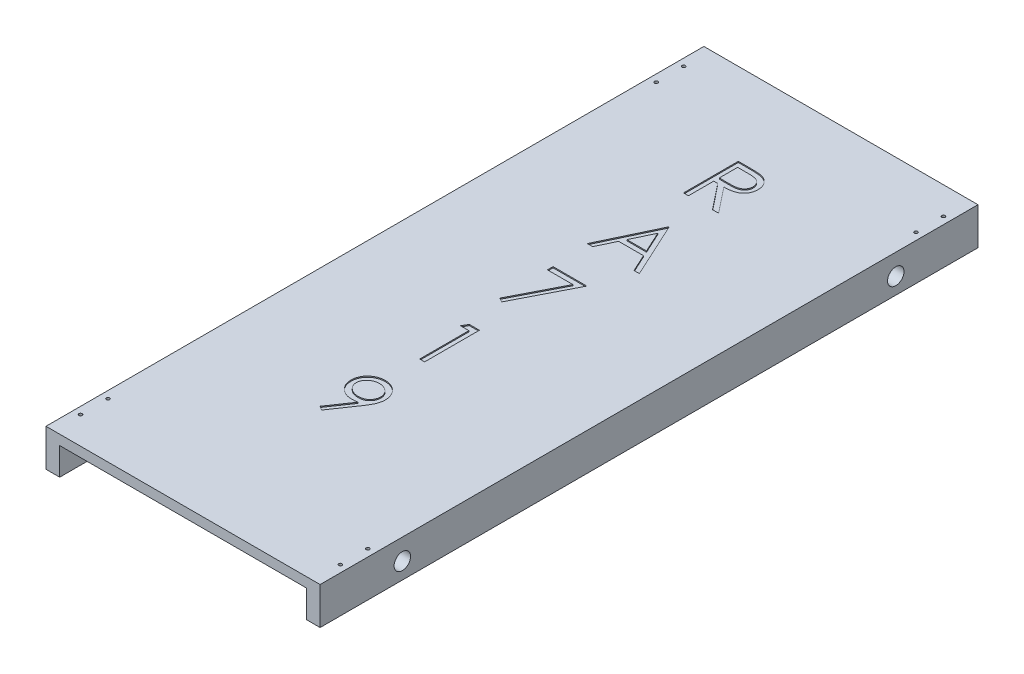
SolidWorks part; units mm, degrees
material "Cedar"
ref_plane "Front Plane" through (0, 0, 0) normal (0, 0, 1) x (1, 0, 0)
ref_plane "Top Plane" through (0, 0, 0) normal (0, 1, 0) x (1, 0, 0)
ref_plane "Right Plane" through (0, 0, 0) normal (1, 0, 0) x (0, 0, -1)
sketch "Sketch2" plane through (0, 0, 0) normal (0, 0, 1) x (1, 0, 0)
  line L0 (0, 0) -> (0, 68)
  line L1 (0, 68) -> (500, 68)
  line L2 (0, 0) -> (25, 0)
  line L3 (25, 50) -> (475, 50)
  line L4 (25, 50) -> (25, 0)
  line L5 (500, 68) -> (500, 0)
  line L6 (500, 0) -> (475, 0)
  line L7 (475, 0) -> (475, 50)
  dimension "D1" = 68
  dimension "D2" = 500
  dimension "D3" = 25
  dimension "D4" = 50
  dimension "D5" = 68
  dimension "D6" = 25
  dimension "D7" = 50
extrude "Boss-Extrude1" add sketch "Sketch2" along normal blind 1200
sketch "Sketch3" plane through (500, 0, 0) normal (1, 0, 0) x (0, 0, -1)
  line L1 (-1200, 0) -> (0, 0) construction
  line L2 (-1200, 0) -> (-1200, 68) construction
  line L3 (0, 0) -> (0, 68) construction
  circle A0 centre (-1050, 30) radius 15
  circle A1 centre (-150, 30) radius 15
  dimension "D1" = 30
  dimension "D3" = 30
  dimension "D4" = 30
  dimension "D2" = 150
  dimension "D5" = 150
  dimension "D6" = 30
extrude "Cut-Extrude1" cut sketch "Sketch3" against normal through all
sketch "Sketch4" plane through (0, 68, 0) normal (0, 1, 0) x (1, 0, 0)
  line L0 (0, -1200) -> (0, 0) construction
  line L1 (500, 0) -> (0, 0) construction
  text T0 "R\r\nA\r\n7\r\n1\r\n9" font "Century Gothic" height 100
  dimension "D1" = 200
  dimension "D2" = 250
extrude "Cut-Extrude2" cut sketch "Sketch4" against normal blind 2
sketch "Sketch5" plane through (0, 50, 0) normal (0, -1, 0) x (1, 0, 0)
  line L0 (0, 1200) -> (0, 0) construction
  line L1 (25, 1200) -> (475, 1200) construction
  text T0 "R\r\nA\r\n7\r\n1\r\n9" font "Century Gothic" height 100
  dimension "D1" = 200
  dimension "D2" = 250
extrude "Cut-Extrude3" cut sketch "Sketch5" against normal blind 2
hole_wizard "Ø6.0 (6) Diameter Hole1" positions "Sketch8" profile "Sketch7" hole size "Ø6.0" standard "ISO" end condition through all
sketch "Sketch8" plane through (0, 0, 0) normal (0, -1, 0) x (-1, 0, 0)
  line L0 (-475, -1200) -> (-500, -1200) construction
  line L1 (-500, -1200) -> (-500, 0) construction
  line L2 (-475, 0) -> (-500, 0) construction
  line L3 (0, 0) -> (-25, 0) construction
  line L4 (0, -1200) -> (0, 0) construction
  line L5 (0, -1200) -> (-25, -1200) construction
  point P0 (-487, -1150)
  point P8 (-487, -1100)
  point P11 (-487, -50)
  point P13 (-487, -100)
  point P18 (-13, -50)
  point P20 (-13, -100)
  point P27 (-13, -1150)
  point P29 (-13, -1100)
  dimension "D1" = 50
  dimension "D2" = 13
  dimension "D3" = 100
  dimension "D4" = 13
  dimension "D5" = 50
  dimension "D6" = 100
  dimension "D7" = 13
  dimension "D8" = 13
  dimension "D9" = 50
  dimension "D10" = 100
  dimension "D11" = 13
  dimension "D12" = 13
  dimension "D13" = 50
  dimension "D14" = 100
  dimension "D15" = 13
  dimension "D16" = 13
sketch "Sketch7" plane through (487, 0, 1150) normal (1, 0, 0) x (0, 0, -1)
  line L0 (0, 0) -> (0, 68)
  line L1 (0, 68) -> (3, 68)
  line L2 (3, 68) -> (3, 0.025)
  line L3 (3, 0.025) -> (3.025, 0)
  line L5 (3.025, 0) -> (0, 0)
  line L6 (-3, 0.025) -> (-3.025, 0) construction
  line L11 (0, -6.35) -> (0, 107.95) construction
  dimension "Thru Hole Dia." = 6
  dimension "Thru Hole Depth" = 68
  dimension "Near C'Sink Dia." = 6.05
  dimension "Near C'Sink Angle" = 90
